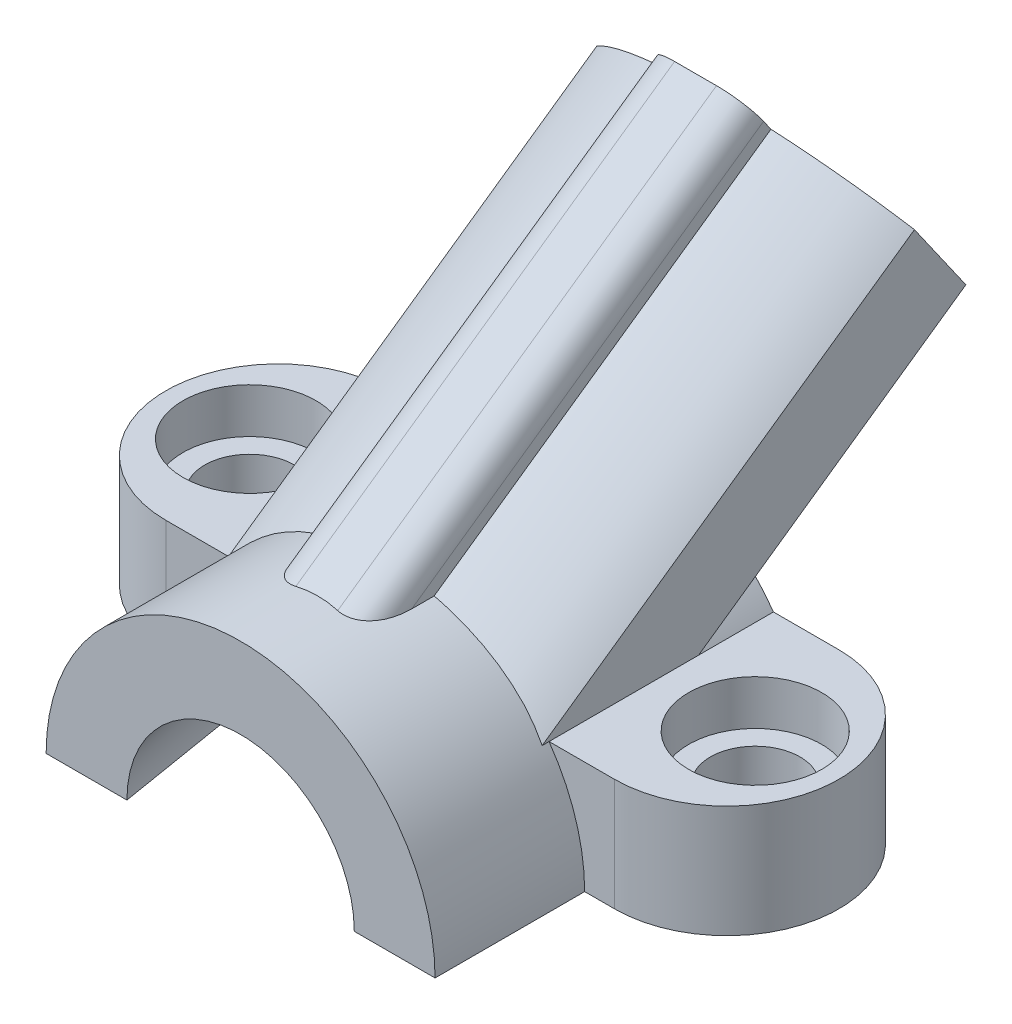
SolidWorks part; units mm, degrees
ref_plane "Front Plane" through (0, 0, 0) normal (0, 0, 1) x (1, 0, 0)
ref_plane "Top Plane" through (0, 0, 0) normal (0, 1, 0) x (1, 0, 0)
ref_plane "Right Plane" through (0, 0, 0) normal (1, 0, 0) x (0, 0, -1)
sketch "Sketch1" plane through (0, 0, 0) normal (0, 0, 1) x (1, 0, 0)
  circle A0 centre (0, 0) radius 13
  dimension "D1" = 26
extrude "Boss-Extrude1" add sketch "Sketch1" against normal blind 25
sketch "Sketch2" plane through (0, 0, 0) normal (1, 0, 0) x (0, 0, -1)
  line L0 (0, 0) -> (0, 7.6)
  line L1 (0, 13) -> (0, -13) construction
  line L2 (0, 7.6) -> (11.5, 9.5)
  line L3 (11.5, 9.5) -> (14, 10.6)
  line L5 (25, -13) -> (25, 13) construction
  line L6 (25, 11) -> (25, 0)
  line L7 (25, 0) -> (0, 0)
  line L8 (14, 10.6) -> (25, 11)
  dimension "D1" = 7.6
  dimension "D2" = 9.5
  dimension "D3" = 10.6
  dimension "D4" = 11
  dimension "D5" = 11
  dimension "D6" = 13.5
revolve "Cut-Revolve1" cut sketch "Sketch2" angle 360 about L7
sketch "Sketch3" plane through (0, 0, 0) normal (0, 1, 0) x (1, 0, 0)
  line L0 (-13, 25) -> (-13, 10)
  line L1 (-13, 25) -> (-13, 0) construction
  line L2 (-13, 10) -> (-15, 10)
  line L3 (-13, 25) -> (-15, 25)
  line L4 (0, 0) -> (0, 26.1438) construction
  line L8 (13, 25) -> (15, 25)
  line L9 (13, 10) -> (15, 10)
  line L10 (13, 25) -> (13, 10)
  arc A0 (-15, 10) -> (-15, 25) centre (-15, 17.5) cw
  arc A2 (15, 10) -> (15, 25) centre (15, 17.5) ccw
  point P16 (-13, 10)
  dimension "D1" = 15
  dimension "D2" = 2
extrude "Boss-Extrude2" add sketch "Sketch3" along normal mid plane 15
sketch "Sketch4" plane through (0, 0, -25) normal (0, 0, -1) x (-1, 0, 0)
  line L11 (-13, 7.5) -> (-13, -7.5)
  line L12 (-13, -7.5) -> (-8.0467, -7.5)
  line L14 (13, 7.5) -> (13, -7.5)
  line L20 (-8.0467, 7.5) -> (-13, 7.5)
  line L21 (13, -7.5) -> (8.0467, -7.5)
  line L23 (8.0467, 7.5) -> (13, 7.5)
  arc A6 (-8.0467, 7.5) -> (-8.0467, -7.5) centre (0, 0) ccw
  circle A7 centre (0, 0) radius 11 construction
  arc A9 (8.0467, -7.5) -> (8.0467, 7.5) centre (0, 0) ccw
extrude "Boss-Extrude3" add sketch "Sketch4" against normal blind 15
sketch "Sketch5" plane through (0, 7.5, 0) normal (0, 1, 0) x (1, 0, 0)
  circle A2 centre (16.9, 17.5) radius 3
  arc A7 (15, 10) -> (15, 25) centre (15, 17.5) ccw construction
  circle A8 centre (-16.9, 17.5) radius 3
  arc A9 (-15, 25) -> (-15, 10) centre (-15, 17.5) ccw construction
  point P10 (22.5, 17.5)
  point P11 (-22.5, 17.5)
  point P12 (0, 0)
  dimension "D1" = 6
  dimension "D2" = 5.6
  dimension "D3" = 5.6
extrude "Cut-Extrude1" cut sketch "Sketch5" against normal through all
sketch "Sketch6" plane through (0, 7.5, 0) normal (0, 1, 0) x (1, 0, 0)
  circle A0 centre (-16.9, 17.5) radius 4.45
  circle A1 centre (16.9, 17.5) radius 4.45
  circle A2 centre (-16.9, 17.5) radius 3 construction
  circle A3 centre (16.9, 17.5) radius 3 construction
  dimension "D1" = 8.9
extrude "Cut-Extrude2" cut sketch "Sketch6" against normal blind 3
sketch "Sketch7" plane through (0, -7.5, 0) normal (0, -1, 0) x (1, 0, 0)
  circle A0 centre (-16.9, -17.5) radius 4
  circle A1 centre (16.9, -17.5) radius 4
  circle A2 centre (-16.9, -17.5) radius 3 construction
  dimension "D1" = 8
extrude "Cut-Extrude3" cut sketch "Sketch7" against normal blind 7.5
sketch "Sketch8" plane through (0, 0, 0) normal (0, 1, 0) x (1, 0, 0)
  point P0 (0, 25.7)
  point P1 (0, 0)
  dimension "D1" = 25.7
ref_plane "Plane1" through (0, 7.1659, -10.2339) normal (0, 0.5736, -0.8192) x (1, 0, 0)
ref_plane "Plane2" through (0, 24.3732, -34.8085) normal (0, 0.5736, -0.8192) x (1, 0, 0)
ref_axis "Axis1" through (0, 0, -25.7) along (0, 0.5736, -0.8192)
sketch "Sketch9" plane through (0, 24.3732, -34.8085) normal (0, 0.5736, -0.8192) x (1, 0, 0)
  line L0 (-10.62, 5.324) -> (10.62, 5.324)
  line L1 (-10.62, 5.324) -> (-10.62, -0.6699)
  line L2 (10.62, 5.324) -> (10.62, -0.6699)
  line L3 (-21.2787, 0) -> (21.2787, 0) construction
  line L4 (-1.4, -7.666) -> (1.4, -7.666)
  line L6 (3.4, -4.8074) -> (3.4, -5.666)
  line L7 (-3.4, -4.8074) -> (-3.4, -5.666)
  arc A0 (-10.62, -0.6699) -> (-3.4, -4.8074) centre (0, 9.494) ccw
  arc A1 (3.4, -4.8074) -> (10.62, -0.6699) centre (0, 9.494) ccw
  arc A2 (-3.4, -5.666) -> (-1.4, -7.666) centre (-1.4, -5.666) ccw
  arc A3 (1.4, -7.666) -> (3.4, -5.666) centre (1.4, -5.666) ccw
  point P0 (0, 9.494)
  point P5 (0, 5.324)
  point P12 (0, 0)
  dimension "D3" = 14.7
  dimension "D9" = 2
  dimension "D1" = 21.24
  dimension "D2" = 4.17
  dimension "D4" = 5.324
  dimension "D5" = 12.99
  dimension "D7" = 3.4
  dimension "D8" = 6.8
extrude "Boss-Extrude6" add sketch "Sketch9" against normal up to next
sketch "Sketch10" plane through (0, 24.3732, -34.8085) normal (0, 0.5736, -0.8192) x (-1, 0, 0)
  line L0 (-10.62, -5.324) -> (10.62, -5.324) construction
  line L1 (-10.62, 0.6699) -> (-10.62, -5.324) construction
  circle A0 centre (-4, -0.484) radius 1.6
  circle A1 centre (4, -0.484) radius 1.6
  point P8 (0, 0)
  dimension "D3" = 6.62
  dimension "D4" = 3.2
  dimension "D1" = 4.84
  dimension "D2" = 8
extrude "Cut-Extrude4" cut sketch "Sketch10" against normal through all
ref_plane "Plane3" through (0, 18.6374, -26.617) normal (0, 0.5736, -0.8192) x (1, 0, 0)
sketch "Sketch11" plane through (0, 18.6374, -26.617) normal (0, 0.5736, -0.8192) x (1, 0, 0)
  circle A0 centre (4, 0.484) radius 3.1
  circle A1 centre (-4, 0.484) radius 3.1
  circle A2 centre (-4, 0.484) radius 1.6 construction
  circle A3 centre (4, 0.484) radius 1.6 construction
  point P8 (0, 0)
  dimension "D1" = 6.2
extrude "Cut-Extrude5" cut sketch "Sketch11" against normal through all
sketch "Sketch12" plane through (0, 0, 0) normal (0, 1, 0) x (1, 0, 0)
  line L0 (0, 0) -> (0, 55.5084) construction
  line L1 (-25, 39.0176) -> (25, 39.0176)
  line L2 (-25, 39.0176) -> (-25, -10.9824)
  line L3 (-25, -10.9824) -> (25, -10.9824)
  line L4 (25, 39.0176) -> (25, -10.9824)
  dimension "D1" = 50
  dimension "D2" = 50
  dimension "D3" = 25
extrude "Cut-Extrude8" cut sketch "Sketch12" against normal through all
equation "\"D8@Sketch9\" = \"D7@Sketch9\" * 2"
equation "\"D3@Sketch5\" = \"D2@Sketch5\""
